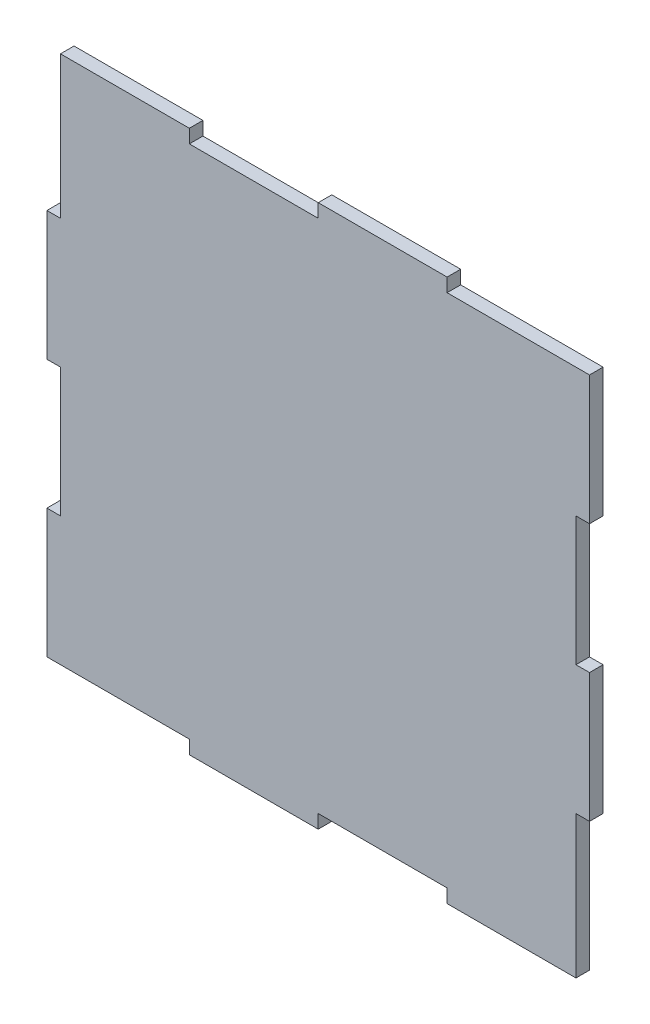
SolidWorks part; units mm, degrees
ref_plane "Front Plane" through (0, 0, 0) normal (0, 0, 1) x (1, 0, 0)
ref_plane "Top Plane" through (0, 0, 0) normal (0, 1, 0) x (1, 0, 0)
ref_plane "Right Plane" through (0, 0, 0) normal (1, 0, 0) x (0, 0, -1)
sketch "Sketch1" plane through (0, 0, 0) normal (0, 0, 1) x (1, 0, 0)
  line L0 (-60.325, 60.325) -> (-60.325, 63.5)
  line L13 (63.5, -63.5) -> (-63.5, -63.5) construction
  line L15 (63.5, -63.5) -> (63.5, 63.5) construction
  line L16 (63.5, 63.5) -> (-63.5, 63.5) construction
  line L17 (-63.5, -63.5) -> (-63.5, 63.5) construction
  line L18 (63.5, -63.5) -> (-63.5, 63.5) construction
  line L19 (63.5, 63.5) -> (-63.5, -63.5) construction
  line L20 (-60.325, 63.5) -> (-30.1625, 63.5)
  line L21 (-30.1625, 63.5) -> (-30.1625, 60.325)
  line L22 (-30.1625, 60.325) -> (0, 60.325)
  line L23 (0, 60.325) -> (0, 63.5)
  line L24 (0, 63.5) -> (30.1625, 63.5)
  line L25 (30.1625, 63.5) -> (30.1625, 60.325)
  line L26 (30.1625, 60.325) -> (60.325, 60.325)
  line L27 (60.325, 60.325) -> (63.5, 60.325)
  line L28 (63.5, 60.325) -> (63.5, 30.1625)
  line L29 (63.5, 30.1625) -> (60.325, 30.1625)
  line L30 (60.325, 30.1625) -> (60.325, 0)
  line L31 (60.325, 0) -> (63.5, 0)
  line L32 (63.5, 0) -> (63.5, -30.1625)
  line L33 (63.5, -30.1625) -> (60.325, -30.1625)
  line L34 (60.325, -30.1625) -> (60.325, -60.325)
  line L35 (60.325, -60.325) -> (60.325, -63.5)
  line L36 (60.325, -63.5) -> (30.1625, -63.5)
  line L37 (30.1625, -63.5) -> (30.1625, -60.325)
  line L38 (30.1625, -60.325) -> (0, -60.325)
  line L39 (0, -60.325) -> (0, -63.5)
  line L40 (0, -63.5) -> (-30.1625, -63.5)
  line L41 (-30.1625, -63.5) -> (-30.1625, -60.325)
  line L42 (-30.1625, -60.325) -> (-60.325, -60.325)
  line L43 (-60.325, -60.325) -> (-63.5, -60.325)
  line L44 (-63.5, -60.325) -> (-63.5, -30.1625)
  line L45 (-63.5, -30.1625) -> (-60.325, -30.1625)
  line L46 (-60.325, -30.1625) -> (-60.325, 0)
  line L47 (-60.325, 0) -> (-63.5, 0)
  line L48 (-63.5, 0) -> (-63.5, 30.1625)
  line L49 (-63.5, 30.1625) -> (-60.325, 30.1625)
  line L50 (-60.325, 30.1625) -> (-60.325, 60.325)
  point P0 (0, 0)
  point P45 (0, 0)
  dimension "D1" = 127
  dimension "D2" = 30.1625
  dimension "D3" = 3.175
  dimension "D5" = 3.175
  dimension "D4" = 2
  dimension "D6" = 4
extrude "Boss-Extrude1" add sketch "Sketch1" along normal blind 3.175 contours L20 L21 L22 L23 L24 L25 L26 L27 L28 L29 L30 L31 L32 L33 L34 L35 L36 L37 L38 L39 L40 L41 L42 L43 L44 L45 L46 L47 L48 L49 L50 L0
equation "\"Notches\"= 2'Number of fitted notches per side"
equation "\"Panel_Thickness\"= .125in'Thickness of panel"
equation "\"Panel_Length\" = 5in'Length of side of panel"
equation "\"D1@Sketch1\"=\"Panel_Length\""
equation "\"D2@Sketch1\"=((\"Panel_Length\"-(\"Panel_Thickness\"*2))/2)/(\"Notches\")"
equation "\"D3@Sketch1\"=\"Panel_Thickness\""
equation "\"D5@Sketch1\"=\"Panel_Thickness\""
equation "\"D1@Boss-Extrude1\"=\"Panel_Thickness\""
